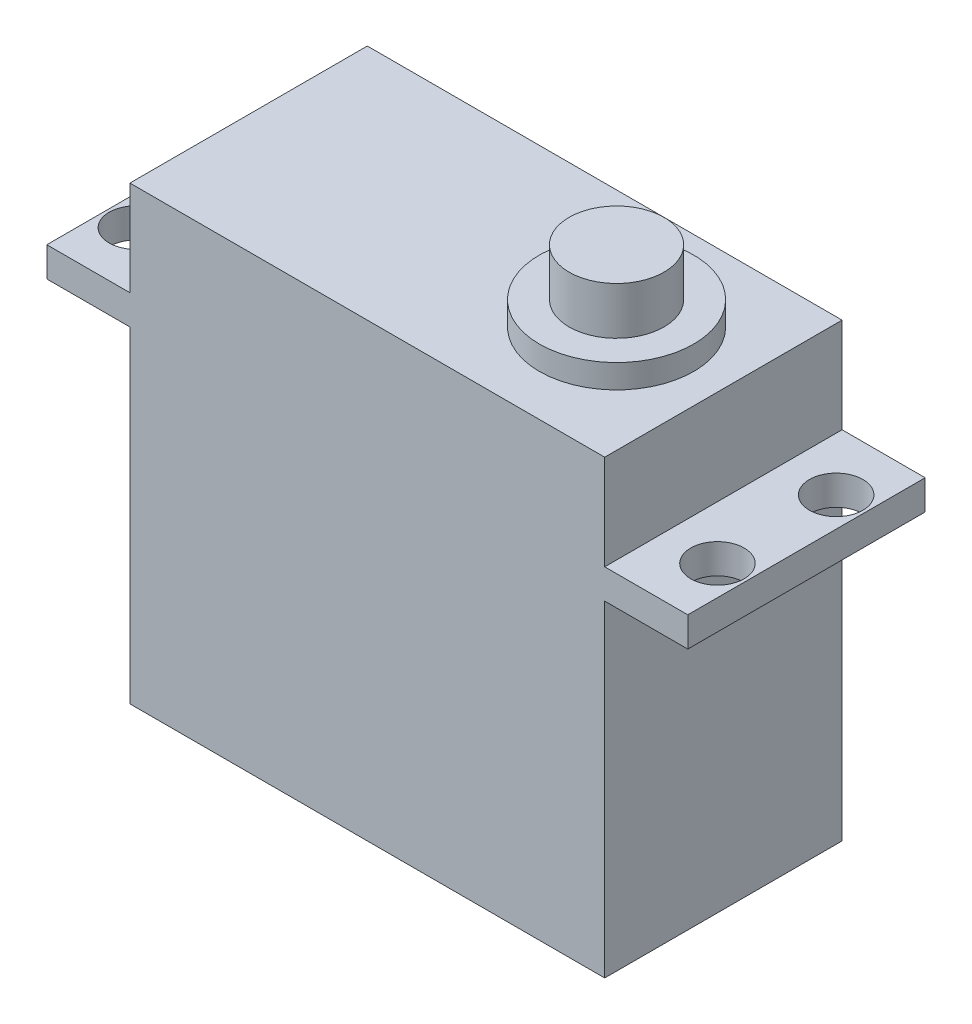
SolidWorks part; units mm, degrees
ref_plane "Front Plane" through (0, 0, 0) normal (0, 0, 1) x (1, 0, 0)
ref_plane "Top Plane" through (0, 0, 0) normal (0, 1, 0) x (1, 0, 0)
ref_plane "Right Plane" through (0, 0, 0) normal (1, 0, 0) x (0, 0, -1)
sketch "Sketch1" plane through (0, 0, 0) normal (0, 1, 0) x (1, 0, 0)
  line L1 (9, 10) -> (-31, 10)
  line L2 (9, 10) -> (9, -10)
  line L3 (9, -10) -> (-31, -10)
  line L4 (-31, 10) -> (-31, -10)
  circle A0 centre (0, 0) radius 4
  point P4 (9, 0)
  dimension "D4" = 8
  dimension "D1" = 40
  dimension "D2" = 20
  dimension "D3" = 9
extrude "Boss-Extrude1" add sketch "Sketch1" against normal blind 38 contours A0 | L1 L4 L3 L2 A0 region at (-11.7375, 0, 0) region at (0, 0, 0)
extrude "Boss-Extrude2" add sketch "Sketch1<3>" along normal blind 6 contours A0
sketch "Sketch1<3>" plane through (0, 0, 0) normal (0, 1, 0) x (1, 0, 0) same geometry as "Sketch1"
ref_axis "Axis1" through (0, 6, 0) along (0, -1, 0)
sketch "Sketch2" plane through (0, 0, 0) normal (0, 1, 0) x (1, 0, 0)
  circle A0 centre (0, 0) radius 6.5
  dimension "D1" = 13
extrude "Boss-Extrude3" add sketch "Sketch2" along normal blind 2
ref_plane "Plane1" through (0, -8, 0) normal (0, -1, 0) x (-1, 0, 0)
ref_plane "Plane2" through (-11, 0, 0) normal (1, 0, 0) x (0, 0, -1)
sketch "Sketch3" plane through (0, -8, 0) normal (0, -1, 0) x (-1, 0, 0)
  line L0 (-9, -10) -> (31, -10) construction
  line L1 (-9, 10) -> (-16, 10)
  line L2 (-9, 10) -> (-9, -10)
  line L3 (-9, -10) -> (-16, -10)
  line L4 (-16, 10) -> (-16, -10)
  line L5 (-13.5, -5) -> (-13.5, 5) construction
  circle A0 centre (-13.5, 5) radius 2.25
  circle A1 centre (-13.5, -5) radius 2.25
  point P11 (-13.5, 0)
  point P12 (-13.957, -4.9951)
  dimension "D2" = 4.5
  dimension "D1" = 7
  dimension "D3" = 10
  dimension "D4" = 4.5
extrude "Boss-Extrude4" add sketch "Sketch3" along normal blind 2.5 separate body
mirror "Mirror1" about plane through (-11, 0, 0) normal (1, 0, 0) of bodies 104
combine bodies "Combine1" operation type add bodies to combine 105 103 104
